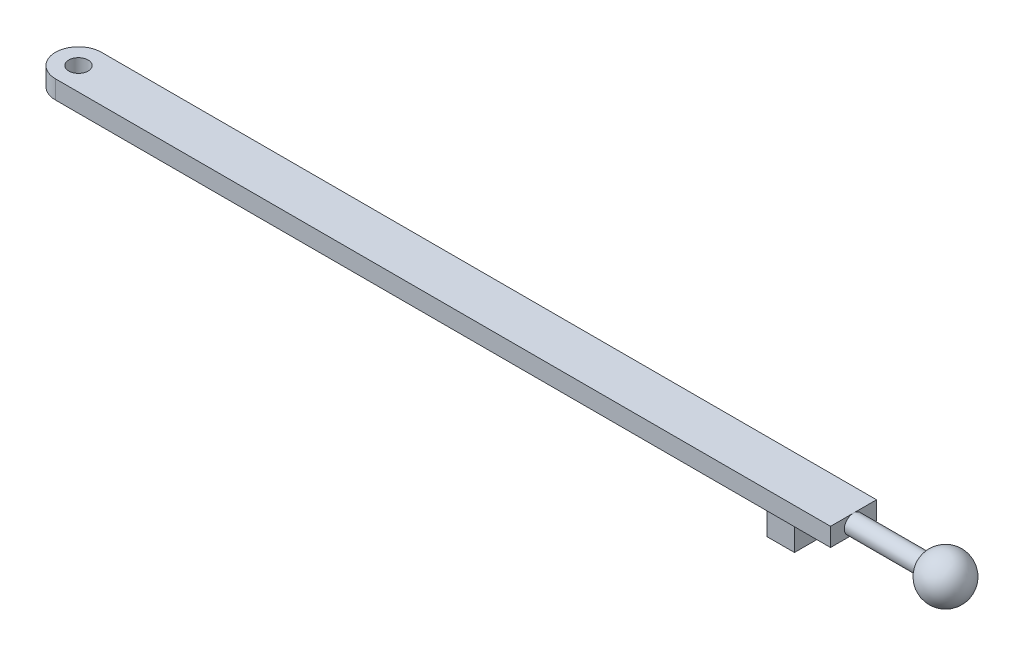
SolidWorks part; units mm, degrees
ref_plane "Front Plane" through (0, 0, 0) normal (0, 0, 1) x (1, 0, 0)
ref_plane "Top Plane" through (0, 0, 0) normal (0, 1, 0) x (1, 0, 0)
ref_plane "Right Plane" through (0, 0, 0) normal (1, 0, 0) x (0, 0, -1)
sketch "Sketch1" plane through (0, 0, 0) normal (0, 1, 0) x (1, 0, 0)
  line L0 (-10, 0) -> (0, 0) construction
  line L1 (-10, 2.5) -> (0, 2.5)
  line L2 (-10, -2.5) -> (0, -2.5)
  line L3 (0, 2.5) -> (0, -2.5)
  arc A0 (-10, 2.5) -> (-10, -2.5) centre (-10, 0) ccw
  circle A3 centre (-10, 0) radius 1
  point P3 (0, 0)
  dimension "D3" = 2
  dimension "D4" = 2.5
  dimension "D5" = 10
  dimension "D6" = 2.5
  dimension "D2" = 5
  dimension "D7" = 10
  dimension "D12" = 10
extrude "Boss-Extrude1" add sketch "Sketch1" along normal blind 2
sketch "Sketch2" plane through (0, 0, 0) normal (0, 0, 1) x (1, 0, 0)
  line L1 (0.0125, 0) -> (-0.0002, 0)
  line L5 (-10, 0) -> (0, 0) construction
  point P2 (0.0125, 1)
  dimension "D2" = 0
sketch "Sketch4" plane through (0, 0, 0) normal (1, 0, 0) x (0, 0, -1)
  circle A0 centre (0, 1) radius 1
  point P0 (0, 1)
extrude "Boss-Extrude2" add sketch "Sketch4" along normal blind 11
sketch "Sketch11" plane through (0, 0, 0) normal (0, -1, 0) x (1, 0, 0)
  line L1 (-7.9973, 0.4701) -> (-7.4489, 0.4701)
  line L2 (-7.9973, 0.4701) -> (-7.9973, -0.2612)
  line L3 (-7.9973, -0.2612) -> (-7.4489, -0.2612)
  line L4 (-7.4489, 0.4701) -> (-7.4489, -0.2612)
extrude "Boss-Extrude3" add sketch "Sketch11" along normal blind 1
sketch "Sketch12" plane through (0, -1, 0) normal (0, -1, 0) x (1, 0, 0)
  line L1 (-8.4784, 0.9317) -> (-5.4924, 0.9317)
  line L2 (-8.4784, 0.9317) -> (-8.4784, -1.8676)
  line L3 (-8.4784, -1.8676) -> (-5.4924, -1.8676)
  line L4 (-5.4924, 0.9317) -> (-5.4924, -1.8676)
extrude "Boss-Extrude4" add sketch "Sketch12" along normal blind 3
sketch "Sketch15" plane through (0, 0, 0) normal (1, 0, 0) x (0, 0, -1)
  line L1 (2.5, 0) -> (-2.5, 0)
  line L2 (2.5, 0) -> (2.5, 2)
  line L3 (2.5, 2) -> (-2.5, 2)
  line L4 (-2.5, 0) -> (-2.5, 2)
extrude "Boss-Extrude5" add sketch "Sketch15" against normal blind 86.79
sketch "Sketch16" plane through (0, 0, 0) normal (0, -1, 0) x (1, 0, 0)
  line L0 (-86.79, 0) -> (-86.79, 2.5)
  line L1 (-84.29, 5.1318) -> (-84.29, -4.4134) construction
  line L2 (-88.1253, 0) -> (-80.4547, 0) construction
  line L3 (0, -2.5) -> (-86.79, -2.5) construction
  line L4 (-84.29, 2.5) -> (-84.29, -2.5)
  line L5 (-86.79, 2.5) -> (-86.79, -2.5) construction
  line L6 (-84.29, 2.5) -> (-86.79, 2.5)
  arc A0 (-84.29, -2.5) -> (-84.29, 2.5) centre (-84.29, 0) cw
  arc A1 (-86.79, 0) -> (-84.29, 2.5) centre (-84.29, 0) cw
  point P6 (-84.29, 0)
  line M3 (0, 2.5) -> (-86.79, 2.5)
  line M4 (-86.79, 2.5) -> (-86.79, -2.5)
  line M5 (-86.79, -2.5) -> (0, -2.5)
  dimension "D1" = 2.5
  dimension "D2" = 2.5
extrude "Cut-Extrude4" cut sketch "Sketch16" against normal through all both contours A0 M5 M3 M4 region at (-86.2316, 0, -1.9416)
sketch "Sketch19" plane through (0, 2, 0) normal (0, 1, 0) x (1, 0, 0)
  circle A0 centre (-84.29, 0) radius 1.05
  dimension "D1" = 2.1
extrude "Cut-Extrude5" cut sketch "Sketch19" against normal through all both
extrude "Cut-Extrude7" cut sketch "Sketch16<4>" against normal through all both contours A0 M4 M3 region at (-86.2316, 0, 1.9416)
sketch "Sketch16<4>" plane through (0, 0, 0) normal (0, -1, 0) x (1, 0, 0) same geometry as "Sketch16"
ref_plane "Plane1" through (0, 1, 0) normal (0, -1, 0) x (-1, 0, 0)
sketch "Sketch22" plane through (0, 1, 0) normal (0, -1, 0) x (-1, 0, 0)
  line L0 (-11, -1) -> (0, -1) construction
  line L1 (0, 1) -> (-11, 1) construction
  line L2 (-11, 1) -> (-11, -1) construction
  line L3 (-10, 1) -> (-10, -1) construction
  line L4 (-12.5, 0) -> (-7.5, 0)
  arc A0 (-10, -1) -> (-10, 1) centre (-10, 0) cw construction
  arc A1 (-7.5, 0) -> (-12.5, 0) centre (-10, 0) cw
  dimension "D1" = 1
  dimension "D3" = 2.5
  dimension "D2" = 1
  dimension "D4" = 5
revolve "Revolve2" add sketch "Sketch22" angle 360 about L4 region at (10, 1, 1.061)
